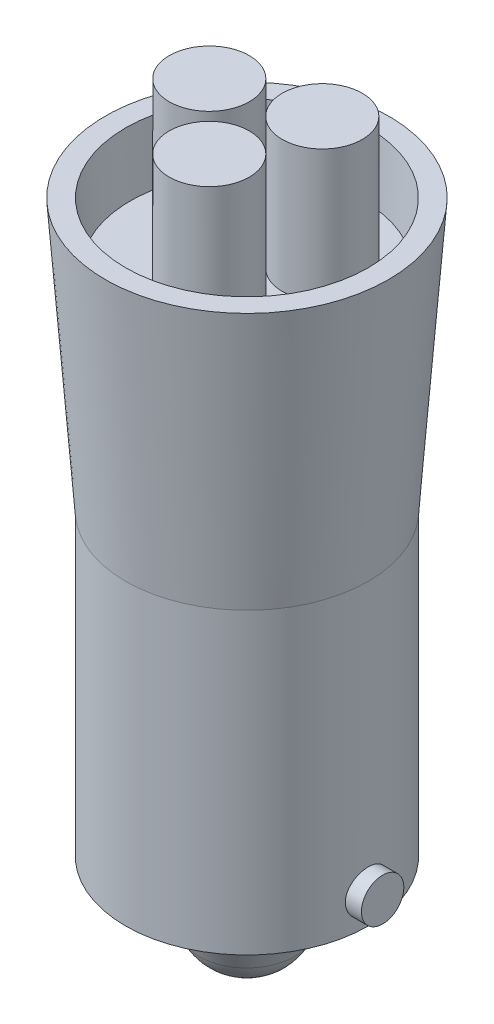
SolidWorks part; units mm, degrees
ref_plane "Front Plane" through (0, 0, 0) normal (0, 0, 1) x (1, 0, 0)
ref_plane "Top Plane" through (0, 0, 0) normal (0, 1, 0) x (1, 0, 0)
ref_plane "Right Plane" through (0, 0, 0) normal (1, 0, 0) x (0, 0, -1)
sketch "Sketch1" plane through (0, 0, 0) normal (0, 0, 1) x (1, 0, 0)
  line L0 (0, 0) -> (0, 22.5724)
  line L1 (1.778, 1.143) -> (2.8639, 3.5224)
  line L2 (2.8639, 3.5224) -> (4.5466, 3.5224)
  line L7 (4.5466, 3.5224) -> (4.5466, 14.6984)
  line L8 (4.5466, 14.6984) -> (5.3022, 24.8584)
  line L9 (5.3022, 24.8584) -> (4.5403, 24.8584)
  line L10 (0, 0) -> (1.778, 0) construction
  line L11 (4.5403, 24.8584) -> (4.3702, 22.5724)
  line L12 (4.3702, 22.5724) -> (0, 22.5724)
  arc A0 (0, 0) -> (1.778, 1.143) centre (0, 1.9544) ccw
  dimension "D1" = 1.778
  dimension "D2" = 1.143
  dimension "D3" = 2.8638
  dimension "D4" = 4.5466
  dimension "D5" = 5.3022
  dimension "D6" = 0.762
  dimension "D7" = 2.286
  dimension "D8" = 11.176
  dimension "D10" = 21.336
revolve "Revolve1" add sketch "Sketch1" angle 360 about L0
sketch "Sketch2" plane through (0, 0, 0) normal (1, 0, 0) x (0, 0, -1)
  line L0 (0, 3.8526) -> (0, 3.5224) construction
  line L1 (-2.8639, 3.5224) -> (2.8639, 3.5224) construction
  circle A0 centre (0, 4.6464) radius 0.7938
  dimension "D1" = 1.5875
  dimension "D2" = 0.3302
extrude "Boss-Extrude1" add sketch "Sketch2" along normal blind 5.08 and the other way blind 5.08
sketch "Sketch3" plane through (0, 22.5724, 0) normal (0, 1, 0) x (1, 0, 0)
  line L0 (0, 0) -> (-1.9264, 0.5162) construction
  line L1 (1.4103, 1.4103) -> (0, 0) construction
  line L2 (0, 0) -> (0.5162, -1.9264) construction
  line L3 (-1.9264, 0.5162) -> (1.4103, 1.4103) construction
  line L4 (1.4103, 1.4103) -> (0.5162, -1.9264) construction
  line L5 (0.5162, -1.9264) -> (-1.9264, 0.5162) construction
  line L6 (0, 0) -> (5.3022, 0) construction
  circle A0 centre (1.4103, 1.4103) radius 1.4986
  circle A1 centre (-1.9264, 0.5162) radius 1.4986
  circle A2 centre (0.5162, -1.9264) radius 1.4986
  circle A3 centre (0, 0) radius 1.9944 construction
  circle A4 centre (0, 0) radius 5.3022 construction
  dimension "D1" = 2.9972
  dimension "D2" = 3.4544
  dimension "D3" = 45
extrude "Boss-Extrude3" add sketch "Sketch3" along normal offset from surface (4.9276 mm away) 2.6416 contours A1 | A0 | A2 region at (1.4103, 22.5724, -1.4103) region at (-1.9264, 22.5724, -0.5162) region at (0.5162, 22.5724, 1.9264) up to face at (4.5403, 24.8584, 0) offset beyond the face yes
